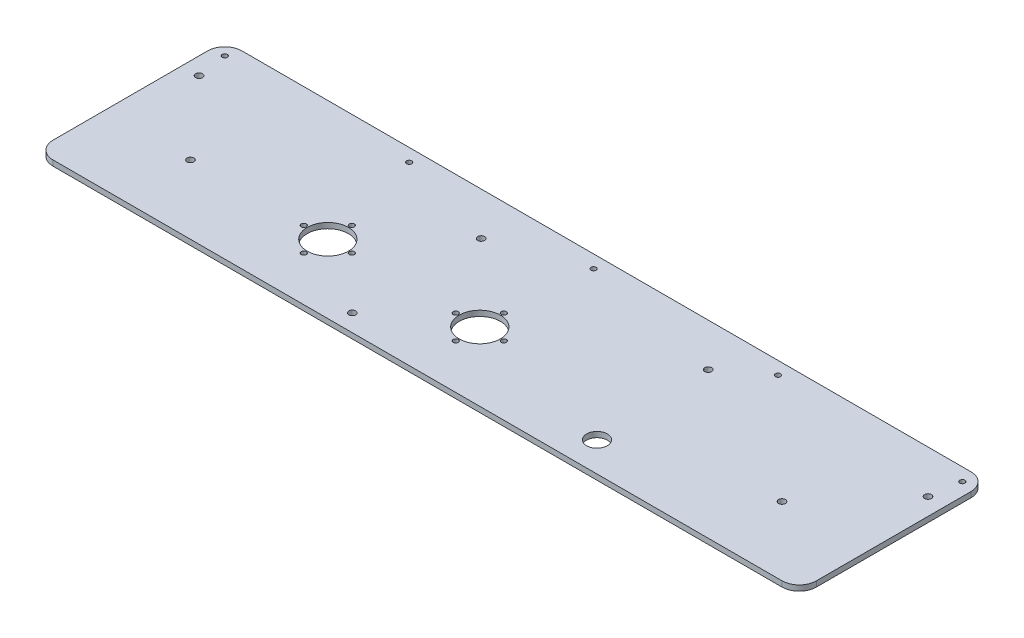
SolidWorks part; units mm, degrees
ref_plane "Front" through (0, 0, 0) normal (0, 0, 1) x (1, 0, 0)
ref_plane "Top" through (0, 0, 0) normal (0, 1, 0) x (1, 0, 0)
ref_plane "Right" through (0, 0, 0) normal (1, 0, 0) x (0, 0, -1)
sketch "Sketch1" plane through (0, 0, 0) normal (0, 1, 0) x (1, 0, 0)
  line L0 (-26.7996, 0) -> (-26.7996, 40)
  line L1 (-26.7996, 0) -> (417.7004, 0)
  line L2 (-26.7996, 0) -> (-26.7996, 110)
  line L3 (-26.7996, 110) -> (417.7004, 110)
  line L4 (417.7004, 0) -> (417.7004, 110)
  line L5 (-26.7996, 40) -> (23.2004, 40)
  line L6 (417.7004, 0) -> (417.7004, 40)
  line L7 (417.7004, 40) -> (367.7004, 40)
  line L8 (23.2004, 40) -> (103.2004, 40)
  line L9 (367.7004, 40) -> (191.7004, 40)
  line L10 (-26.7996, 110) -> (-26.7996, 85)
  line L11 (-26.7996, 85) -> (417.7004, 85)
  line L12 (-26.7996, 85) -> (-16.7996, 85)
  line L13 (417.7004, 85) -> (407.7004, 85)
  line L14 (103.2004, 40) -> (191.7004, 40)
  line L15 (147.4504, 40) -> (147.4504, 85)
  line L16 (279.7004, 40) -> (279.7004, 85)
  line L17 (147.4504, 40) -> (147.4504, 10)
  line L18 (-26.7996, 110) -> (-26.7996, 102.5)
  line L19 (-26.7996, 102.5) -> (417.7004, 102.5)
  line L20 (-26.7996, 102.5) -> (-19.2996, 102.5)
  line L21 (417.7004, 102.5) -> (410.2004, 102.5)
  line L22 (195.4504, 102.5) -> (410.2004, 102.5)
  line L23 (-19.2996, 102.5) -> (195.4504, 102.5)
  line L24 (417.7004, 0) -> (417.7004, 17.2282)
  line L25 (417.7004, 17.2282) -> (282.7004, 17.2282)
  circle A10 centre (367.7004, 40) radius 2
  circle A11 centre (23.2004, 40) radius 2
  circle A12 centre (103.2004, 40) radius 12
  circle A13 centre (103.2004, 40) radius 14
  circle A15 centre (103.2004, 54) radius 1.5
  circle A16 centre (89.2004, 40) radius 1.5
  circle A17 centre (103.2004, 26) radius 1.5
  circle A18 centre (117.2004, 40) radius 1.5
  circle A19 centre (191.7004, 40) radius 12
  circle A20 centre (191.7004, 40) radius 14
  circle A21 centre (191.7004, 26) radius 1.5
  circle A22 centre (205.7004, 40) radius 1.5
  circle A23 centre (191.7004, 54) radius 1.5
  circle A24 centre (177.7004, 40) radius 1.5
  circle A25 centre (-16.7996, 85) radius 2
  circle A26 centre (407.7004, 85) radius 2
  circle A27 centre (147.4504, 85) radius 2
  circle A28 centre (279.7004, 85) radius 2
  circle A29 centre (147.4504, 10) radius 2
  circle A30 centre (195.4504, 102.5) radius 1.5
  circle A31 centre (-19.2996, 102.5) radius 1.5
  circle A32 centre (410.2004, 102.5) radius 1.5
  circle A33 centre (302.8254, 102.5) radius 1.5
  circle A34 centre (88.0754, 102.5) radius 1.5
  circle A35 centre (282.7004, 17.2282) radius 6
  dimension "D3" = 40
  dimension "D7" = 80
  dimension "D8" = 176
  dimension "D9" = 25
  dimension "D11" = 10
  dimension "D12" = 30
  dimension "D13" = 7.5
  dimension "D14" = 7.5
  dimension "D16" = 17.2282
  dimension "D1" = 110
  dimension "D2" = 444.5
  dimension "D4" = 50
  dimension "D5" = 40
  dimension "D6" = 50
  dimension "D10" = 10
  dimension "D15" = 7.5
  dimension "D17" = 135
extrude "Boss-Extrude1" add sketch "Sketch1" along normal blind 3.175 contours A18 L14 A12 L8 A16 A13 A17 | A18 A13 A15 A16 L8 A12 L14 | A24 L14 A19 L9 A22 A20 A23 | A24 A20 A21 A22 L9 A19 L14 | A29 L14 A18 A13 A17 A16 L8 A11 L5 L0 L1 L4 L7 A10 L9 A22 A20 A21 A24 | A28 L11 A27 L15 L14 A24 A20 A23 A22 L9 L16 | A27 L11 A25 L2 L5 A11 L8 A16 A13 A15 A18 L14 L15 | A28 L11 A26 L13 L4 L3 L2 A25 A27 | A28 L16 L9 A10 L7 L4 L13 A26 L11 | A34 L23 A30 L22 A33 A32 L21 L4 L3 L10 L19 A31 region at (196.684, 0, -19.4923) region at (58.5861, 0, -63.184) region at (195.421, 0, -93.7571) region at (195.4504, 0, -106.2666) region at (348.6559, 0, -62.489) region at (93.521, 0, -49.6794) region at (90.515, 0, -38.754) region at (214.7998, 0, -63.4004) region at (204.3858, 0, -41.246) region at (201.3798, 0, -30.3206)
fillet "Fillet1" radius 10 4 edges at (417.7004, 1.5875, -110) (417.7004, 1.5875, 0) (-26.7996, 1.5875, 0) (-26.7996, 1.5875, -110)
